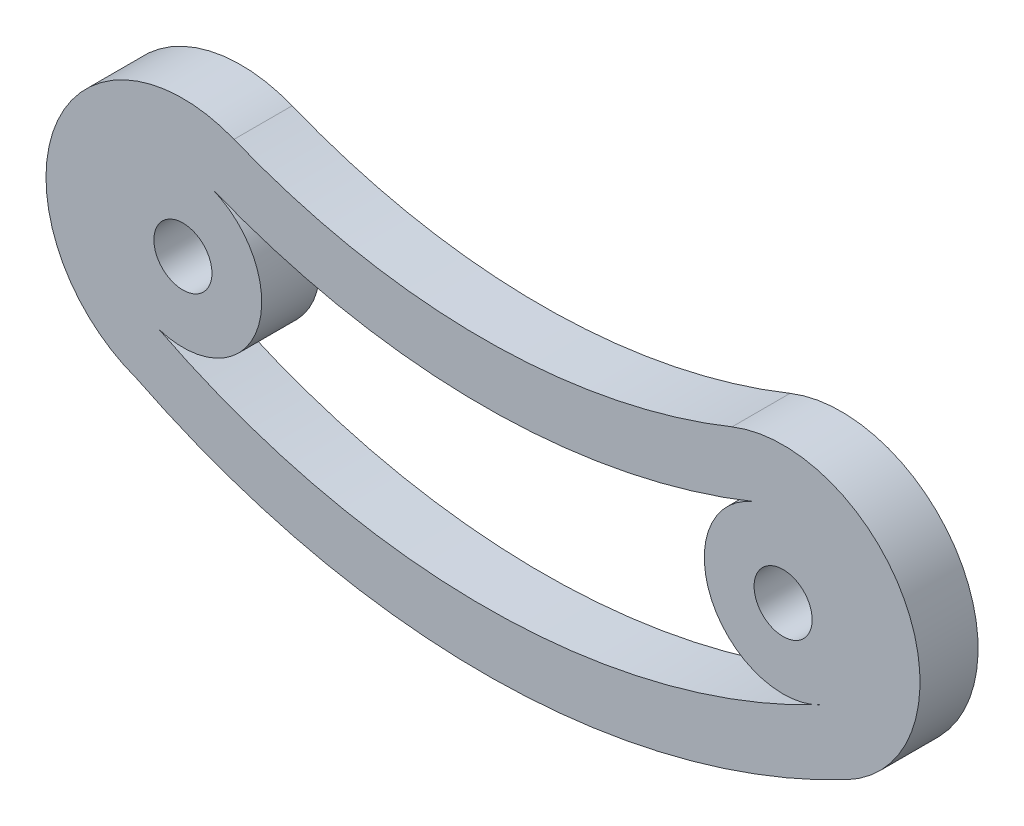
SolidWorks part; units mm, degrees
material "1060 Alloy"
ref_plane "Front Plane" through (0, 0, 0) normal (0, 0, 1) x (1, 0, 0)
ref_plane "Top Plane" through (0, 0, 0) normal (0, 1, 0) x (1, 0, 0)
ref_plane "Right Plane" through (0, 0, 0) normal (1, 0, 0) x (0, 0, -1)
sketch "Sketch1" plane through (0, 0, 0) normal (0, 0, 1) x (1, 0, 0)
  line L0 (0, 0) -> (31, 0)
  line L1 (0, -5) -> (31, -5)
  line L2 (0, 5) -> (31, 5)
  circle A0 centre (31, 0) radius 1.5
  circle A1 centre (0, 0) radius 1.5
  arc A2 (0, -5) -> (0, 5) centre (0, 0) cw
  arc A3 (31, -5) -> (31, 5) centre (31, 0) ccw
  dimension "D1" = 3
extrude "Extrude1" add sketch "Sketch1" along normal blind 3 contours L1 A3 L2 A2 A1 A0 region at (-4.578, 0, 0)
sketch "Sketch2" plane through (0, 0, 3) normal (0, 0, 1) x (1, 0, 0)
  line L1 (15.5, 5) -> (15.5, -10)
  line L2 (0, 5) -> (31, 5) construction
  arc A0 (36, 0) -> (-5, 0) centre (15.5, 16.0125) cw
  arc A1 (36, 0) -> (31, 5) centre (33.5, 2.5) ccw
  arc A2 (31, -5) -> (31, 5) centre (31, 0) ccw construction
  arc A3 (0, 5) -> (0, -5) centre (0, 0) ccw construction
  arc A4 (31, 5) -> (0, 5) centre (15.5, 21.0125) cw
  arc A5 (-5, 0) -> (0, 5) centre (-2.5, 2.5) cw
  line M3 (0, -5) -> (31, -5)
  arc M4 (31, -5) -> (31, 5) centre (31, 0) ccw
  line M5 (31, 5) -> (0, 5)
  arc M6 (0, 5) -> (0, -5) centre (0, 0) ccw
  dimension "D2" = 5
  dimension "D1" = 15
extrude "Boss-Extrude2" add sketch "Sketch2" against normal blind 3 contours A1 M4 | A0 L1 M3 | A0 L1 M3 | A5 M6 region at (21.3318, -7.0174, 3) region at (9.6682, -7.0174, 3) region at (34.927, 3.927, 3) region at (-3.927, 3.927, 3)
extrude "Cut-Extrude4" cut sketch "Sketch2<6>" against normal blind 5 contours A0 M4 M3 | A0 M3 M6 | A4 L1 M5 | A4 L1 M5 region at (21.4396, 2.4578, 3) region at (9.5604, 2.4578, 3) region at (33.916, -3.0126, 3) region at (-2.916, -3.0126, 3)
sketch "Sketch2<6>" plane through (0, 0, 3) normal (0, 0, 1) x (1, 0, 0) same geometry as "Sketch2"
sketch "Sketch5" plane through (0, 0, 0) normal (0, 0, -1) x (-1, 0, 0)
  circle A0 centre (0, 0) radius 7.0711
  circle A1 centre (-31, 0) radius 7.0711
  arc M7 (0, 5) -> (-31, 5) centre (-15.5, 21.0125) cw
  arc M8 (-31, 5) -> (-36, 0) centre (-33.5, 2.5) ccw
  arc M9 (-36, 0) -> (5, 0) centre (-15.5, 16.0125) ccw
  arc M10 (5, 0) -> (0, 5) centre (2.5, 2.5) ccw
extrude "Boss-Extrude3" add sketch "Sketch5" against normal blind 3 contours A1 M7 M8 | A1 M8 M9 | A0 M10 M7 | A0 M9 M10 region at (-3.5179, -3.3541, 0) region at (2.7948, 4.3745, 0) region at (34.5179, -3.3541, 0) region at (28.2052, 4.3745, 0)
sketch "Sketch6" plane through (0, 0, 0) normal (0, 0, -1) x (-1, 0, 0)
  arc A0 (-2.6395, 6.5599) -> (-28.3605, 6.5599) centre (-15.5, 38.5218) cw
  arc A1 (-2.5997, -6.5758) -> (-7.0605, 0.3867) centre (0, 0) ccw construction
  arc A2 (-23.9395, 0.3867) -> (-28.4003, -6.5758) centre (-31, 0) ccw construction
  arc A3 (2.3961, -6.6527) -> (-34.2887, -6.2598) centre (-15.5624, 29.3845) cw
  arc M1 (-23.9395, 0.3867) -> (-28.4003, -6.5758) centre (-31, 0) ccw
  arc M2 (-28.4003, -6.5758) -> (-2.5997, -6.5758) centre (-15.5, 16.0125) ccw
  arc M3 (-2.5997, -6.5758) -> (-7.0605, 0.3867) centre (0, 0) ccw
  arc M4 (-7.0605, 0.3867) -> (-23.9395, 0.3867) centre (-15.5, 21.0125) cw
extrude "Boss-Extrude4" add sketch "Sketch6" against normal blind 3 contours A0 M3 M1 M4 | A3 M3 M2 M1 region at (15.5, 2.0626, 0) region at (15.9897, -10.5074, 0)
sketch "Sketch7" plane through (0, 0, 0) normal (0, 0, -1) x (-1, 0, 0)
  circle A4 centre (-31, 0) radius 4.0711
  circle A5 centre (0, 0) radius 4.0711
  arc A8 (-32.8934, -3.604) -> (1.2332, -3.8798) centre (-15.5624, 29.3845) ccw
  arc A9 (-32.8934, -3.604) -> (1.2332, -3.8798) centre (-15.5624, 29.3845) ccw
  arc A10 (1.2332, -3.8798) -> (-1.5197, 3.7768) centre (0, 0) ccw
  arc A11 (1.2332, -3.8798) -> (-1.5197, 3.7768) centre (0, 0) ccw
  arc A12 (-29.4803, 3.7768) -> (-1.5197, 3.7768) centre (-15.5, 38.5218) ccw
  arc A13 (-29.4803, 3.7768) -> (-1.5197, 3.7768) centre (-15.5, 38.5218) ccw
  arc A14 (-29.4803, 3.7768) -> (-32.8934, -3.604) centre (-31, 0) ccw
  arc A15 (-29.4803, 3.7768) -> (-32.8934, -3.604) centre (-31, 0) ccw
  dimension "D1" = 3
extrude "Cut-Extrude6" cut sketch "Sketch7" against normal blind 5 contours A13 A4 A9 A5 region at (15.5258, -2.8514, 0)
move or copy body "Body-Move/Copy1" [suppressed] bodies to move or copy 112
move or copy body "Body-Move/Copy2" [suppressed] bodies to move or copy 112
